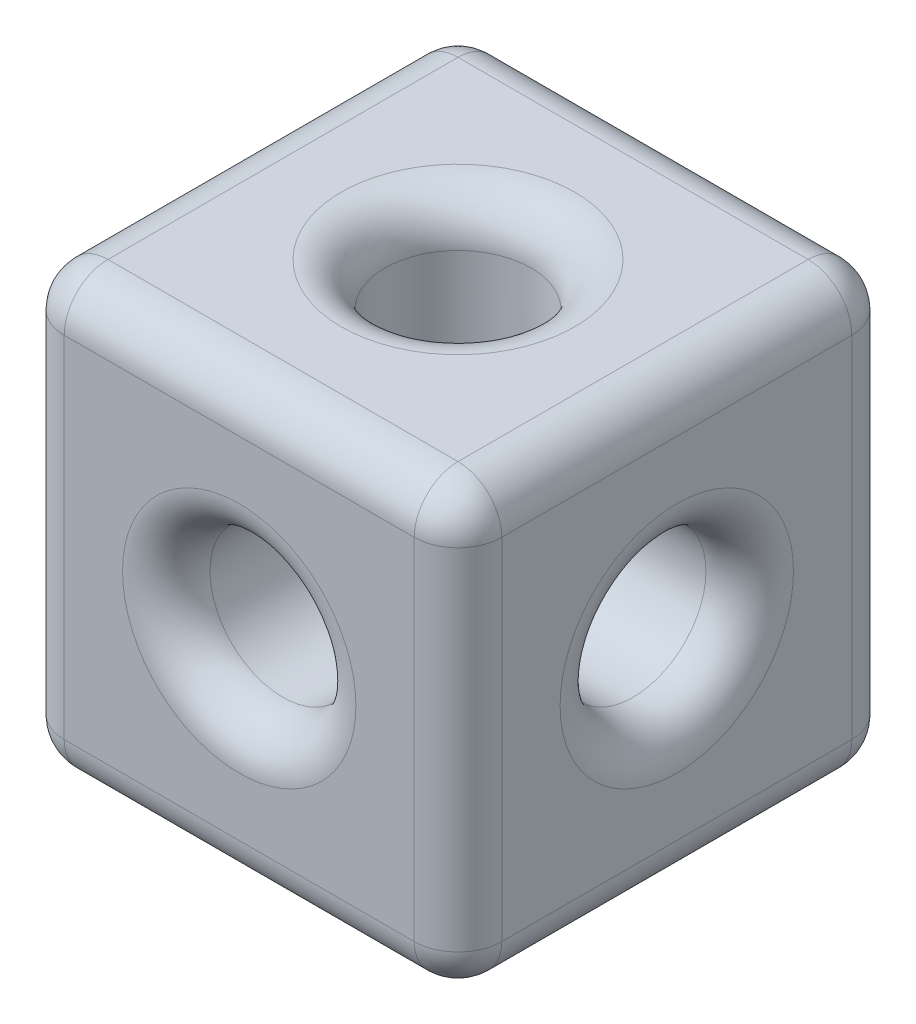
SolidWorks part; units mm, degrees
ref_plane "前视基准面" through (0, 0, 0) normal (0, 0, 1) x (1, 0, 0)
ref_plane "上视基准面" through (0, 0, 0) normal (0, 1, 0) x (1, 0, 0)
ref_plane "右视基准面" through (0, 0, 0) normal (1, 0, 0) x (0, 0, -1)
sketch "草图1" plane through (0, 0, 0) normal (0, 1, 0) x (1, 0, 0)
  line L5 (-3, -3) -> (3, -3)
  line L6 (-3, -3) -> (-3, 3)
  line L7 (-3, 3) -> (3, 3)
  line L8 (3, -3) -> (3, 3)
  line L9 (0, 3) -> (0, -3) construction
  line L10 (-3, 0) -> (3, 0) construction
  point P0 (0, 0)
  dimension "D1" = 6
  dimension "D2" = 6
extrude "凸台-拉伸1" add sketch "草图1" along normal blind 3 and the other way blind 3
sketch "草图2" plane through (0, 0, 3) normal (0, 0, 1) x (1, 0, 0)
  circle A0 centre (0, 0) radius 1
  dimension "D1" = 2
extrude "切除-拉伸1" cut sketch "草图2" against normal through all
sketch "草图3" plane through (3, 0, 0) normal (1, 0, 0) x (0, 0, -1)
  circle A0 centre (0, 0) radius 1
  dimension "D1" = 2
extrude "切除-拉伸2" cut sketch "草图3" against normal through all
sketch "草图4" plane through (0, 3, 0) normal (0, 1, 0) x (1, 0, 0)
  circle A0 centre (0, 0) radius 1
  dimension "D1" = 2
extrude "切除-拉伸3" cut sketch "草图4" against normal through all
fillet "圆角1" radius 0.6 18 edges at (3, -3, 0) (3, 0, -1) (0, -3, -3) (3, 0, -3) (1, 0, -3) (-3, -3, 0) (-3, 0, -3) (-3, 0, -1) (0, -3, 3) (-3, 0, 3) (3, 0, 3) (1, 0, 3) (0, 3, 3) (-3, 3, 0) (0, 3, -3) (3, 3, 0) (0, 3, 1) (0, -3, 1)
